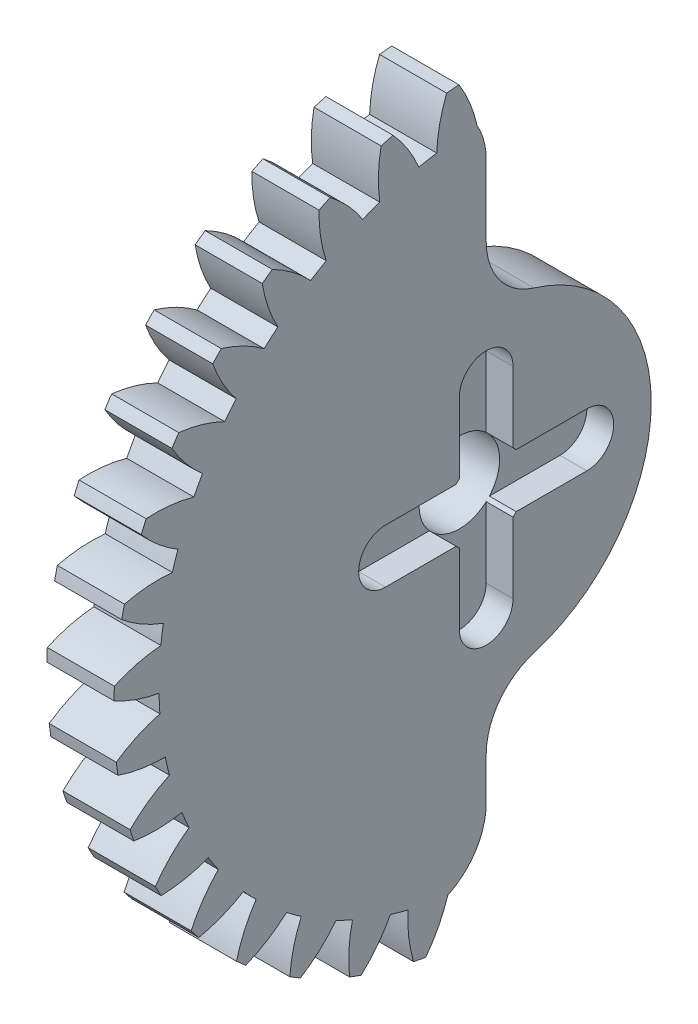
SolidWorks part; units mm, degrees
ref_plane "Plane1" through (0, 0, 0) normal (0, 0, 1) x (1, 0, 0)
ref_plane "Plane2" through (0, 0, 0) normal (0, 1, 0) x (1, 0, 0)
ref_plane "Plane3" through (0, 0, 0) normal (1, 0, 0) x (0, 0, -1)
sketch "HoldingSke" plane through (0, 0, 0) normal (0, 1, 0) x (1, 0, 0)
  line L0 (0, 0) -> (0.5461, -0.3824)
  line L1 (-15, 0) -> (100, 0) construction
  line L2 (0, 0) -> (-2.1039, 2.3779)
  line L3 (0, 0) -> (-11.863, 4.5341)
  line L4 (0, 0) -> (7.0742, 4.9534)
  line L5 (0, 0) -> (-46.8476, -17.4728)
  line L6 (0, 0) -> (-5.8027, -3.9151)
  line L7 (-2.1039, 2.3779) -> (8.6586, 51.2059)
  line L8 (-76.2, 54.61) -> (-75.2, 54.61)
  line L9 (-71.009, 38.7566) -> (-53.1078, 45.2721)
  line L10 (-76.2, 71.12) -> (104.1128, 71.12)
  line L11 (0, 0) -> (-7, 0)
  line L12 (-76.2, 101.6) -> (-76.147, 101.6)
  line L13 (24.9733, 27.94) -> (52.9518, 28.4284)
  line L14 (24.9733, 27.94) -> (24.9743, 27.94)
  line L15 (24.9733, 27.94) -> (100.4006, 29.5858)
  line L16 (-63.627, -1.5) -> (-12.827, -1.5)
  circle A0 centre (0, 0) radius 3
  circle A1 centre (0, 0) radius 24.374
  circle A2 centre (0, 0) radius 37.5
  circle A3 centre (0, 0) radius 3
  dimension "Num_teeth" = 35
  dimension "Pitch_radius" = 180.3128
  dimension "Width" = 7
  dimension "Thickness" = 7
sketch "BasProSke" plane through (0, 0, 0) normal (0, 1, 0) x (1, 0, 0)
  line L0 (-10, 0) -> (60, 0) construction
  line L1 (0, 0) -> (0, 27.75)
  line L2 (0, 0) -> (7, 0)
  line L3 (7, 0) -> (7, 27.75)
  line L4 (7, 27.75) -> (0, 27.75)
  dimension "Thickness" = 7
  dimension "Diameter" = 55.5
revolve "Base-Revolve" add sketch "BasProSke" angle 360 about L0
sketch "TooCutSke" plane through (0, 0, 0) normal (1, 0, 0) x (0, 0, -1)
  line L1 (0, 0) -> (0, 107) construction
  line L2 (0, 0) -> (-1.2704, 26.2192) construction
  line L3 (0, 0) -> (-4.702, 52.244) construction
  line L4 (-1.2704, 26.2192) -> (-2.351, 26.122) construction
  arc A0 (0.6781, 24.3646) -> (-0.6781, 24.3646) centre (0, 0) ccw
  arc A1 (2.0444, 27.7001) -> (-2.0444, 27.7001) centre (0, 0) ccw
  circle A2 centre (0, 0) radius 26.25 construction
  circle A3 centre (0, 0) radius 24.6669 construction
  arc A4 (-0.6781, 24.3646) -> (-2.0444, 27.7001) centre (-10.9336, 22.1114) ccw
  arc A5 (2.0444, 27.7001) -> (0.6781, 24.3646) centre (10.9336, 22.1114) ccw
extrude "ToothCut" cut sketch "TooCutSke" along normal through all
fillet "Breaks" [suppressed] radius 0.03 tangent propagation no
fillet "RootFillets" [suppressed] radius 0.376
pattern_circular "TeethCuts" count 35 every 10.286 about axis through (-10, 0, 0) along (1, 0, 0) of "ToothCut", "RootFillets", "Breaks"
sketch "HubNeaOneSke" plane through (0, 0, 0) normal (-1, 0, 0) x (0, 0, 1)
  circle A0 centre (0, 0) radius 24.374
  dimension "Diameter" = 48.748
extrude "HubNearOne" [suppressed] add sketch "HubNeaOneSke" along normal blind 43.0001
sketch "HubNeaBotSke" plane through (0, 0, 0) normal (-1, 0, 0) x (0, 0, 1)
  circle A0 centre (0, 0) radius 24.374
  dimension "Diameter" = 48.748
extrude "HubNearBoth" [suppressed] add sketch "HubNeaBotSke" along normal blind 21.5
ref_plane "FarPln" through (7, 0, 0) normal (1, 0, 0) x (0, 0, -1)
sketch "HubFarSke" plane through (7, 0, 0) normal (1, 0, 0) x (0, 0, -1)
  circle A0 centre (0, 0) radius 24.374
  dimension "Diameter" = 48.748
extrude "HubFar" [suppressed] add sketch "HubFarSke" along normal blind 21.5
sketch "BorSke" plane through (0, 0, 0) normal (1, 0, 0) x (0, 0, -1)
  circle A0 centre (0, 0) radius 3
  dimension "Diameter" = 6
extrude "Bore" cut sketch "BorSke" along normal mid plane 100.0001
sketch "KeySke" plane through (0, 0, 0) normal (1, 0, 0) x (0, 0, -1)
  line L0 (-1, 0) -> (-1, 4)
  line L1 (-1, 4) -> (1, 4)
  line L2 (1, 4) -> (1, 0)
  line L3 (0, 0) -> (0, 34) construction
  line L4 (-1, 0) -> (1, 0)
  dimension "Width" = 2
extrude "Keyway" [suppressed] cut sketch "KeySke" along normal mid plane 100.0001
pattern_circular "Keyway2" [suppressed] count 2 every 90 about axis through (-10, 0, 0) along (1, 0, 0) reverse direction yes
sketch "Sketch3" plane through (7, 0, 0) normal (1, 0, 0) x (0, 0, -1)
  line L0 (-1.5, -7.5) -> (-1.5, 7.5)
  line L1 (1.5, 7.5) -> (1.5, -7.5)
  arc A0 (-1.5, 7.5) -> (1.5, 7.5) centre (0, 7.5) cw
  arc A1 (1.5, -7.5) -> (-1.5, -7.5) centre (0, -7.5) cw
  circle A2 centre (0, 0) radius 3 construction
  point P6 (0, 9)
  point P7 (0, -9)
  dimension "D1" = 1.5
  dimension "D2" = 18
  dimension "D4" = 1.5
  dimension "D3" = 9
extrude "Cut-Extrude1" cut sketch "Sketch3" against normal blind 2
sketch "Sketch4" plane through (7, 0, 0) normal (1, 0, 0) x (0, 0, -1)
  line L0 (-7.5, 1.5) -> (7.5, 1.5)
  line L1 (7.5, -1.5) -> (-7.5, -1.5)
  arc A0 (7.5, 1.5) -> (7.5, -1.5) centre (7.5, 0) cw
  arc A1 (-7.5, -1.5) -> (-7.5, 1.5) centre (-7.5, 0) cw
  arc A2 (1.5, -2.5981) -> (1.5, 2.5981) centre (0, 0) ccw construction
  point P5 (-9, 0)
  point P7 (9, 0)
  dimension "D1" = 1.5
  dimension "D2" = 18
  dimension "D3" = 9
  dimension "D4" = 1.5
extrude "Cut-Extrude2" cut sketch "Sketch4" against normal blind 2
sketch "Sketch5" plane through (7, 0, 0) normal (1, 0, 0) x (0, 0, -1)
  line L0 (0, -12.2978) -> (0, -32.4838)
  line L1 (0, 33.1623) -> (0, 12.2978)
  circle A0 centre (0, 0) radius 12.2978
  arc A1 (0, -32.4838) -> (0, 33.1623) centre (0, 0.3393) ccw
extrude "Cut-Extrude3" cut sketch "Sketch5" against normal blind 10 contours L0 A1 L1 A0 region at (7, 0.3947, -15.3531)
sketch "Sketch6" plane through (7, 0, 0) normal (1, 0, 0) x (0, 0, -1)
  line L0 (-2, 2) -> (-2, 7.5)
  line L1 (2, 7.5) -> (2, 2)
  line L2 (2, 2) -> (7.5, 2)
  line L3 (7.5, -2) -> (2, -2)
  line L4 (2, -2) -> (2, -7.5)
  line L5 (-2, -7.5) -> (-2, -2)
  line L6 (-2, -2) -> (-7.5, -2)
  line L7 (-7.5, 2) -> (-2, 2)
  line L8 (1.5, -7.5) -> (1.5, -2.5981) construction
  line L9 (7.5, 1.5) -> (2.5981, 1.5) construction
  line L11 (-2.5981, 1.5) -> (-7.5, 1.5) construction
  line L12 (-1.5, 7.5) -> (-1.5, 2.5981) construction
  arc A0 (-2, 7.5) -> (2, 7.5) centre (0, 7.5) cw
  arc A1 (7.5, 2) -> (7.5, -2) centre (7.5, 0) cw
  arc A2 (2, -7.5) -> (-2, -7.5) centre (0, -7.5) cw
  arc A3 (-7.5, -2) -> (-7.5, 2) centre (-7.5, 0) cw
  arc A4 (7.5, -1.5) -> (7.5, 1.5) centre (7.5, 0) ccw construction
  arc A5 (-1.5, -7.5) -> (1.5, -7.5) centre (0, -7.5) ccw construction
  arc A6 (-7.5, 1.5) -> (-7.5, -1.5) centre (-7.5, 0) ccw construction
  arc A7 (1.5, 7.5) -> (-1.5, 7.5) centre (0, 7.5) ccw construction
  point P18 (9.5, 0)
  point P27 (0, -9.5)
  point P30 (-9.5, 0)
  point P37 (0, 9.5)
  dimension "D1" = 2
  dimension "D4" = 2
  dimension "D5" = 0.5
  dimension "D6" = 2
  dimension "D8" = 2
  dimension "D10" = 2
  dimension "D12" = 2
  dimension "D2" = 0.5
  dimension "D3" = 2
  dimension "D7" = 0.5
  dimension "D9" = 2
  dimension "D11" = 0.5
extrude "Cut-Extrude4" cut sketch "Sketch6" against normal up to vertex (2 mm away) up to point (5, 1.5, 7.5)
fillet "Fillet2" radius 5 2 edges at (3.5, 12.2978, 0) (3.5, -12.2978, 0)
ref_plane "Plane4" through (0, 24.374, 0) normal (1, 0, 0) x (0, 0, -1)
sketch "Sketch8" plane through (7, 0, 0) normal (1, 0, 0) x (0, 0, -1)
  line L0 (-2.8594, -24.2057) -> (-1.5086, -24.3273)
  line L1 (-1.5086, -24.3273) -> (1.2437, -24.575)
  line L2 (1.2437, -24.575) -> (1.2437, -32.1347)
  line L3 (1.2437, -32.1347) -> (-1.9339, -26.9792)
  line L4 (-1.9339, -26.9792) -> (-2.8594, -24.2057)
extrude "Cut-Extrude5" cut sketch "Sketch8" against normal blind 10
fillet "Fillet3" radius 5 2 edges at (3.5, 24.374, 0) (3.5, -24.463, 0)
sketch "Sketch9" plane through (0, 0, 0) normal (0, 1, 0) x (1, 0, 0)
  line L0 (-2.4485, -28.8785) -> (2, -28.8785)
  line L1 (2, -28.8785) -> (2, 12.9926)
  line L2 (2, 12.9926) -> (-3.9498, 12.9926)
  line L3 (-3.9498, 12.9926) -> (-3.9498, -28.8785)
  line L4 (-3.9498, -28.8785) -> (-2.4485, -28.8785)
  line L5 (0, 12.2978) -> (0, 3.5547) construction
  dimension "D1" = 2
extrude "Cut-Extrude6" cut sketch "Sketch9" against normal through all both and the other way through all
equation "' \"Module@HoldingSke\" = 6.35"
equation "' \"Num_teeth@HoldingSke\" = 12"
equation "' \"Ap@HoldingSke\" =  20"
equation "' \"Ap@HoldingSke\" = 20"
equation "' \"Width@HoldingSke\" = 0.5 * 25.4"
equation "' \"Hub_dia@HoldingSke\"= 1 * 25.4"
equation "' \"Hub_dia@HoldingSke\" = 1 * 25.4"
equation "' \"Overall_len@HoldingSke\" = 1.0 * 25.4"
equation "' \"Bore@HoldingSke\" = 0.75 * 25.4"
equation "' \"T_dim@HoldingSke\" = 0.1 * 25.4"
equation "' \"Width@KeySke\" = 0.25 * 25.4"
equation "' \"Show_teeth@HoldingSke\" = 13"
equation "' \"Backlash@HoldingSke\" = 0.009 * 25.4"
equation "' \"Addendum_fac@HoldingSke\" = 1.0"
equation "' \"Dedendum_fac@HoldingSke\" = 1.25"
equation "' \"Dedendum_add@HoldingSke\" = 0.00005 * 25.4"
equation "' \"Clearance_fac@HoldingSke\" = 0.25"
equation "\"Pitch@HoldingSke\" = 1 / \"Module@HoldingSke\""
equation "\"Overcut_dia@TooCutSke\" = (\"Num_teeth@HoldingSke\" + 2 * \"Addendum_fac@HoldingSke\") / \"Pitch@HoldingSke\" + 0.002 * 25.4"
equation "\"Pitch_dia@TooCutSke\" = \"Num_teeth@HoldingSke\" / \"Pitch@HoldingSke\""
equation "\"Base_dia@TooCutSke\" = \"Num_teeth@HoldingSke\" / \"Pitch@HoldingSke\" * cos((\"Ap@HoldingSke\"  * 3.14159265 / 180))"
equation "\"Root_dia@TooCutSke\" = (\"Num_teeth@HoldingSke\" + 2) / \"Pitch@HoldingSke\" - 2 * (\"Addendum_fac@HoldingSke\" + \"Dedendum_fac@HoldingSke\") / \"Pitch@HoldingSke\" - \"Dedendum_add@HoldingSke\" * 2"
equation "\"Half_ang@TooCutSke\" = 180 / \"Num_teeth@HoldingSke\""
equation "\"Half_CT@TooCutSke\" = \"Num_teeth@HoldingSke\" / \"Pitch@HoldingSke\" * sin((3.14159265 / 2 / \"Num_teeth@HoldingSke\")) / 2 - 7 * \"Backlash@HoldingSke\" / 4"
equation "\"Flank_rad@TooCutSke\" = \"Num_teeth@HoldingSke\" / \"Pitch@HoldingSke\" / 5"
equation "\"Radius@RootFillets\" = \"Clearance_fac@HoldingSke\" / \"Pitch@HoldingSke\" + \"Dedendum_add@HoldingSke\""
equation "\"Break_rad@Breaks\" = 0.02 / \"Pitch@HoldingSke\""
equation "\"Thickness@HoldingSke\" = \"Width@HoldingSke\""
equation "\"OAL@HoldingSke\" = \"Thickness@HoldingSke\""
equation "\"MHD@HoldingSke\" = (\"Num_teeth@HoldingSke\" + 2) / \"Pitch@HoldingSke\" - 2 * (\"Addendum_fac@HoldingSke\" + \"Dedendum_fac@HoldingSke\")  / \"Pitch@HoldingSke\" - \"Dedendum_add@HoldingSke\" * 2"
equation "\"MBD@HoldingSke\" = (\"Num_teeth@HoldingSke\" + 2) / \"Pitch@HoldingSke\" - 2 * (\"Addendum_fac@HoldingSke\" + \"Dedendum_fac@HoldingSke\")  / \"Pitch@HoldingSke\" - \"Dedendum_add@HoldingSke\" * 2 - 0.002 * 25.4"
equation "\"MHD@HoldingSke\" = ((sgn( \"MHD@HoldingSke\" - \"Hub_dia@HoldingSke\" )-1)*( \"MHD@HoldingSke\" - \"Hub_dia@HoldingSke\" ))/-2+ \"Hub_dia@HoldingSke\""
equation "\"MBD@HoldingSke\" = ((sgn( \"MBD@HoldingSke\" - \"Bore@HoldingSke\" )-1)*( \"MBD@HoldingSke\" - \"Bore@HoldingSke\" ))/-2+ \"Bore@HoldingSke\""
equation "\"OAL@HoldingSke\" = ((sgn( \"OAL@HoldingSke\" - \"Overall_len@HoldingSke\" )+1)*( \"OAL@HoldingSke\" - \"Overall_len@HoldingSke\" ))/2 + \"Overall_len@HoldingSke\" + 0.000002 * 25.4"
equation "\"Num_teeth@TeethCuts\" = int( \"Show_teeth@HoldingSke\" ) + 1"
equation "\"Num_teeth@TeethCuts\" = ((sgn( \"Num_teeth@TeethCuts\" - \"Num_teeth@HoldingSke\" )-1)*( \"Num_teeth@TeethCuts\" - \"Num_teeth@HoldingSke\" ))/-2+ \"Num_teeth@HoldingSke\""
equation "\"Num_teeth@TeethCuts\" = ((sgn( \"Num_teeth@TeethCuts\" - 2.0)+1)*( \"Num_teeth@TeethCuts\" - 2.0))/2 +2.0"
equation "\"Angle@TeethCuts\" = 360.0 / \"Num_teeth@HoldingSke\""
equation "\"Diameter@BasProSke\" = (\"Num_teeth@HoldingSke\" + 2 * \"Addendum_fac@HoldingSke\") / \"Pitch@HoldingSke\""
equation "\"Thickness@BasProSke\"  = \"Thickness@HoldingSke\""
equation "' \"Fillet_rad@BasProSke\" =  \"Thickness@HoldingSke\" * 0.05"
equation "' \"Fillet_rad@BasProSke\" = \"Thickness@HoldingSke\" * 0.05"
equation "\"MHD@HoldingSke\" = ((sgn( \"MHD@HoldingSke\" - \"Root_dia@TooCutSke\" )-1)*( \"MHD@HoldingSke\" - \"Root_dia@TooCutSke\" ))/-2+ \"Root_dia@TooCutSke\""
equation "\"Diameter@HubNeaOneSke\" = \"MHD@HoldingSke\""
equation "\"Length@HubNearOne\" = \"OAL@HoldingSke\" - \"Thickness@BasProSke\""
equation "\"Diameter@HubNeaBotSke\" = \"MHD@HoldingSke\""
equation "\"Length@HubNearBoth\" = ( \"OAL@HoldingSke\" - \"Thickness@BasProSke\" ) / 2.0"
equation "\"Thickness@FarPln\" = \"Thickness@BasProSke\""
equation "\"Diameter@HubFarSke\" = \"MHD@HoldingSke\""
equation "\"Length@HubFar\" = ( \"OAL@HoldingSke\" - \"Thickness@BasProSke\" ) / 2.0"
equation "\"Diameter@BorSke\" = \"MBD@HoldingSke\""
equation "\"D1@Bore\" = \"OAL@HoldingSke\" * 2.0"
equation "\"D1@Keyway\" = \"OAL@HoldingSke\" * 2.0"
equation "\"Offset@KeySke\" = \"T_dim@HoldingSke\" + \"MBD@HoldingSke\" / 2.0"
